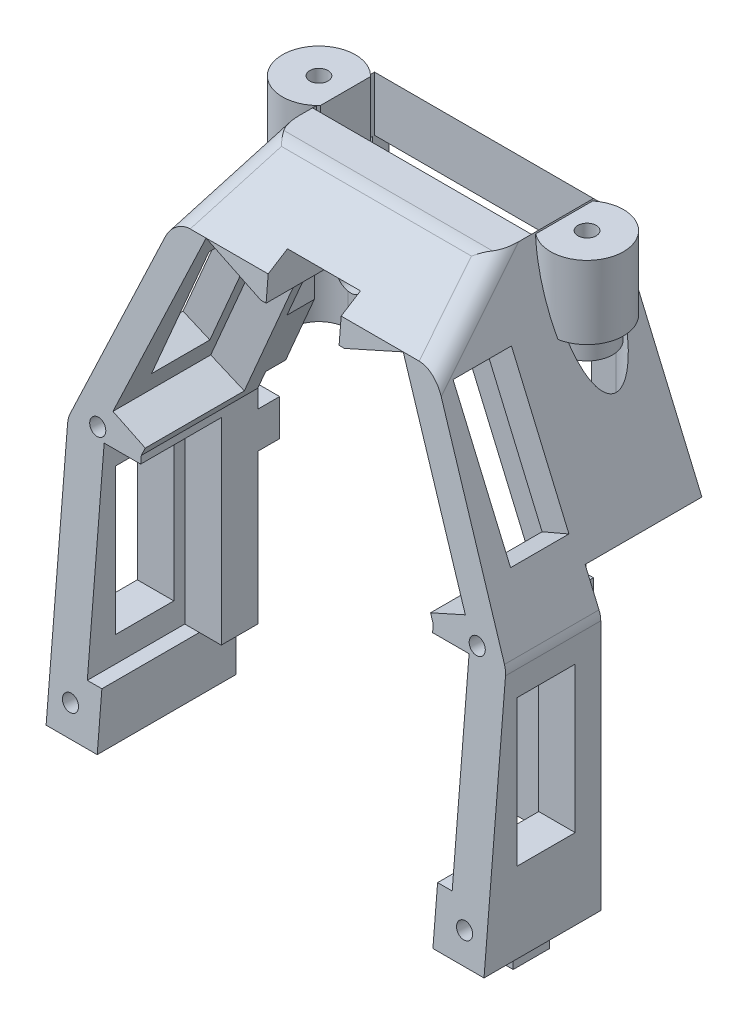
SolidWorks part; units mm, degrees
ref_plane "Front Plane" through (0, 0, 0) normal (0, 0, 1) x (1, 0, 0)
ref_plane "Top Plane" through (0, 0, 0) normal (0, 1, 0) x (1, 0, 0)
ref_plane "Right Plane" through (0, 0, 0) normal (1, 0, 0) x (0, 0, -1)
sketch "Sketch1" plane through (0, 0, 0) normal (0, 0, 1) x (1, 0, 0)
  line L0 (-30, 17.5) -> (-15, 52.5)
  line L2 (-30, -17.5) -> (-30, 17.5)
  line L4 (30, -17.5) -> (30, 17.5)
  line L5 (-30, -17.5) -> (30, 17.5) construction
  line L6 (-30, 17.5) -> (30, -17.5) construction
  line L7 (-15, 52.5) -> (15, 52.5)
  line L8 (15, 52.5) -> (30, 17.5)
  line L9 (-20, -17.5) -> (-20, 15.4474)
  line L10 (-20, 15.4474) -> (-8.406, 42.5)
  line L11 (-8.406, 42.5) -> (8.406, 42.5)
  line L12 (8.406, 42.5) -> (20, 15.4474)
  line L13 (20, -17.5) -> (20, 15.4474)
  line L14 (-30, -17.5) -> (-20, -17.5)
  line L15 (20, -17.5) -> (30, -17.5)
  point P0 (0, 0)
  point P9 (0, 52.5)
  dimension "D1" = 60
  dimension "D2" = 35
  dimension "D3" = 70
  dimension "D4" = 30
  dimension "D5" = 10
extrude "Boss-Extrude1" add sketch "Sketch1" along normal blind 32
sketch "Sketch2" plane through (0, 0, 0) normal (0, 1, 0) x (1, 0, 0)
  line L0 (15, 0) -> (-15, 0) construction
  line L1 (15, -2) -> (-15, -2)
  line L2 (15, -2) -> (15, -10.5)
  line L3 (15, -10.5) -> (-15, -10.5)
  line L4 (-15, -2) -> (-15, -10.5)
  point P9 (0, -2)
  dimension "D1" = 8.5
  dimension "D2" = 2
  dimension "D3" = 30
extrude "Cut-Extrude1" cut sketch "Sketch2" against normal blind 25 from surface starting at face at (0, 52.5, 16)
sketch "Sketch3" plane through (0, 0, 0) normal (0, 1, 0) x (1, 0, 0)
  line L0 (-15, 0) -> (-30, 0) construction
  line L1 (15, -14) -> (-15, -14)
  line L2 (15, -14) -> (15, 0)
  line L3 (15, 0) -> (-15, 0)
  line L4 (-15, -14) -> (-15, 0)
  line L5 (15, -14) -> (-15, 0) construction
  line L6 (15, 0) -> (-15, -14) construction
  line L7 (0, -7) -> (0, 0) construction
  line L8 (18.37, -6.25) -> (-18.37, -6.25) construction
  line L9 (18.37, -10.25) -> (-18.37, -10.25)
  line L10 (18.37, -2.25) -> (-18.37, -2.25)
  line L11 (15, -10.5) -> (-15, -2) construction
  arc A2 (18.37, -10.25) -> (18.37, -2.25) centre (18.37, -6.25) ccw
  arc A3 (-18.37, -2.25) -> (-18.37, -10.25) centre (-18.37, -6.25) ccw
  point P0 (0, -7)
  point P7 (0, -14)
  point P13 (0, -6.25)
  dimension "D4" = 8
  dimension "D3" = 3.37
  dimension "D1" = 30
  dimension "D2" = 14
extrude "Cut-Extrude3" cut sketch "Sketch3" along normal blind 25 from offset 20 contours L9 A3 L10 A2 | L1 L4 L3 L2
sketch "Sketch4" plane through (0, 0, 0) normal (0, 0, 1) x (1, 0, 0)
  line L0 (-8.406, 42.5) -> (8.406, 42.5) construction
  line L1 (-5, 42.5) -> (5, 42.5)
  line L2 (-5, 42.5) -> (-5, 47.5)
  line L3 (-5, 47.5) -> (5, 47.5)
  line L4 (5, 42.5) -> (5, 47.5)
  point P6 (0, 47.5)
  dimension "D1" = 10
  dimension "D2" = 5
extrude "Cut-Extrude4" cut sketch "Sketch4" against normal up to surface (-10.5 mm away) from surface up to face at (0, 48.75, 10.5) starting at face at (0, 15.4912, 32)
sketch "Sketch5" plane through (0, 0, 0) normal (1, 0, 0) x (0, 0, -1)
  line L0 (-32, -17.5) -> (-32, 17.5) construction
  line L1 (-27.5, -6.5) -> (-19.5, -6.5)
  line L2 (-27.5, -6.5) -> (-27.5, 13.5)
  line L3 (-27.5, 13.5) -> (-19.5, 13.5)
  line L4 (-19.5, -6.5) -> (-19.5, 13.5)
  line L5 (-27.5, -6.5) -> (-19.5, 13.5) construction
  line L6 (-27.5, 13.5) -> (-19.5, -6.5) construction
  line L7 (-32, -17.5) -> (0, -17.5) construction
  line L9 (0, -17.5) -> (-13, -17.5)
  line L10 (0, -17.5) -> (0, 20.5)
  line L11 (0, 20.5) -> (-13, 20.5)
  line L12 (-13, -17.5) -> (-13, 20.5)
  point P0 (-23.5, 3.5)
  dimension "D1" = 8
  dimension "D2" = 20
  dimension "D3" = 4.5
  dimension "D4" = 11
  dimension "D5" = 13
  dimension "D6" = 38
extrude "Cut-Extrude5" cut sketch "Sketch5" against normal up to surface (30 mm away) from surface up to face at (-30, 0, 16) starting at face at (30, 0, 16)
sketch "Sketch6" plane through (0, 0, 0) normal (1, 0, 0) x (0, 0, -1)
  line L0 (-27.5, -6.5) -> (-27.5, 13.5) construction
  line L1 (-32, -17.5) -> (-32, 17.5) construction
  line L2 (-18, -10) -> (-32, -10)
  line L3 (-18, -10) -> (-18, 17)
  line L4 (-18, 17) -> (-32, 17)
  line L5 (-32, -10) -> (-32, 17)
  line L6 (-18, -10) -> (-32, 17) construction
  line L7 (-18, 17) -> (-32, -10) construction
  point P4 (-25, 3.5)
  point P11 (-27.5, 3.5)
  dimension "D1" = 27
  dimension "D2" = 14
extrude "Cut-Extrude6" cut sketch "Sketch6" against normal mid plane 50
sketch "Sketch7" plane through (0, 0, 0) normal (1, 0, 0) x (0, 0, -1)
  line L1 (0, -17.5) -> (-16, -17.5)
  line L2 (0, -17.5) -> (0, 22.5)
  line L3 (0, 22.5) -> (-16, 22.5)
  line L4 (-16, -17.5) -> (-16, 22.5)
  line L6 (-32, -17.5) -> (-13, -17.5) construction
  line L7 (0, 52.5) -> (0, 20.5) construction
  dimension "D1" = 16
  dimension "D2" = 40
extrude "Cut-Extrude7" cut sketch "Sketch7" along normal blind 5 from surface starting at face at (-30, 3.5, 23.5)
extrude "Cut-Extrude8" cut sketch "Sketch7<2>" against normal blind 5 from surface starting at face at (30, 3.5, 23.5)
sketch "Sketch7<2>" plane through (0, 0, 0) normal (1, 0, 0) x (0, 0, -1) same geometry as "Sketch7"
ref_plane "Plane1" through (-40.8725, 17.5168, 0) normal (-0.9191, 0.3939, 0) x (0, 0, 1)
sketch "Sketch8" plane through (-40.8725, 17.5168, 0) normal (-0.9191, 0.3939, 0) x (0, 0, 1)
  line L0 (32, 42.3463) -> (32, 4.2675) construction
  line L1 (16.8, 33.3069) -> (24.8, 33.3069)
  line L2 (16.8, 33.3069) -> (16.8, 13.3069)
  line L3 (16.8, 13.3069) -> (24.8, 13.3069)
  line L4 (24.8, 33.3069) -> (24.8, 13.3069)
  line L5 (16.8, 33.3069) -> (24.8, 13.3069) construction
  line L6 (16.8, 13.3069) -> (24.8, 33.3069) construction
  point P0 (20.8, 23.3069)
  point P8 (32, 23.3069)
  dimension "D1" = 8
  dimension "D2" = 20
  dimension "D3" = 7.2
extrude "Cut-Extrude9" cut sketch "Sketch8" against normal blind 15 from surface starting at face at (-19.2921, 42.485, 6.25)
ref_plane "Plane2" through (40.8725, 17.5168, 0) normal (0.9191, 0.3939, 0) x (0, 0, -1)
sketch "Sketch9" plane through (40.8725, 17.5168, 0) normal (0.9191, 0.3939, 0) x (0, 0, -1)
  line L0 (-32, 4.2675) -> (-32, 42.3463) construction
  line L1 (-24.8, 13.3069) -> (-16.8, 13.3069)
  line L2 (-24.8, 13.3069) -> (-24.8, 33.3069)
  line L3 (-24.8, 33.3069) -> (-16.8, 33.3069)
  line L4 (-16.8, 13.3069) -> (-16.8, 33.3069)
  line L5 (-24.8, 13.3069) -> (-16.8, 33.3069) construction
  line L6 (-24.8, 33.3069) -> (-16.8, 13.3069) construction
  point P0 (-20.8, 23.3069)
  point P7 (-32, 23.3069)
  dimension "D1" = 8
  dimension "D2" = 20
  dimension "D3" = 7.2
extrude "Cut-Extrude10" cut sketch "Sketch9" against normal blind 15 from surface starting at face at (19.2921, 42.485, 6.25)
sketch "Sketch11" plane through (-40.8725, 17.5168, 0) normal (-0.9191, 0.3939, 0) x (0, 0, 1)
  line L0 (24.8, 33.3069) -> (24.8, 13.3069) construction
  line L1 (15.3, 36.8069) -> (32, 36.8069)
  line L2 (15.3, 36.8069) -> (15.3, 9.8069)
  line L3 (15.3, 9.8069) -> (32, 9.8069)
  line L4 (32, 36.8069) -> (32, 9.8069)
  line L5 (32, 42.3463) -> (32, 4.2675) construction
  point P6 (24.8, 23.3069)
  point P7 (32, 23.3069)
  dimension "D1" = 27
  dimension "D2" = 16.7
extrude "Cut-Extrude11" cut sketch "Sketch11" against normal blind 15 from offset 14 offset against normal yes
sketch "Sketch12" plane through (40.8725, 17.5168, 0) normal (0.9191, 0.3939, 0) x (0, 0, -1)
  line L1 (-15.3, 9.8069) -> (-32, 9.8069)
  line L2 (-15.3, 9.8069) -> (-15.3, 36.8069)
  line L3 (-15.3, 36.8069) -> (-32, 36.8069)
  line L4 (-32, 9.8069) -> (-32, 36.8069)
  line L5 (-15.3, 9.8069) -> (-32, 36.8069) construction
  line L6 (-15.3, 36.8069) -> (-32, 9.8069) construction
  line L7 (-24.8, 13.3069) -> (-24.8, 33.3069) construction
  line L8 (-32, 4.2675) -> (-32, 42.3463) construction
  point P0 (-23.65, 23.3069)
  point P10 (-24.8, 23.3069)
  dimension "D1" = 27
  dimension "D2" = 16.7
extrude "Cut-Extrude12" cut sketch "Sketch12" against normal blind 16 from offset 14 offset against normal yes
sketch "Sketch13" plane through (0, 0, 0) normal (1, 0, 0) x (0, 0, -1)
  line L0 (-32, 52.5) -> (-26, 52.5)
  line L1 (-32, 52.5) -> (-10.5, 52.5) construction
  line L2 (-26, 52.5) -> (-32, -17.5)
  line L3 (-32, -17.5) -> (-32, 52.5)
  dimension "D1" = 6
extrude "Cut-Extrude13" cut sketch "Sketch13" against normal mid plane 62
sketch "Sketch14" plane through (0, 0, 0) normal (1, 0, 0) x (0, 0, -1)
  line L0 (-16, 52.5) -> (-26, 52.5)
  line L1 (-26, 52.5) -> (-10.5, 52.5) construction
  line L2 (-26, 52.5) -> (-26.5715, 45.8328)
  line L3 (-26.5715, 45.8328) -> (-16, 52.5)
  dimension "D1" = 10
extrude "Cut-Extrude14" cut sketch "Sketch14" against normal mid plane 62
sketch "Sketch16" plane through (0, 0, 0) normal (0, 1, 0) x (1, 0, 0)
  circle A0 centre (18.37, -6.25) radius 3.5
  circle A1 centre (-18.37, -6.25) radius 3.5
  circle A2 centre (18.37, -6.25) radius 1.25
  circle A3 centre (-18.37, -6.25) radius 1.25
  arc A4 (-18.37, -2.25) -> (-18.37, -10.25) centre (-18.37, -6.25) ccw construction
  arc A5 (18.37, -10.25) -> (18.37, -2.25) centre (18.37, -6.25) ccw construction
  dimension "D1" = 2.5
  dimension "D2" = 2.5
  dimension "D3" = 7
extrude "Boss-Extrude2" add sketch "Sketch16" against normal blind 5.5 from surface starting at face at (16.6071, 45, 6.25)
ref_plane "Plane3" through (0, 3.4492, 40.241) normal (0, 0.0854, 0.9963) x (1, 0, 0)
sketch "Sketch17" plane through (0, 3.4492, 40.241) normal (0, 0.0854, 0.9963) x (1, 0, 0)
  line L1 (-30, -20.1689) -> (-20, -20.1689) construction
  line L2 (-30, -20.1689) -> (-30, 14.9594) construction
  line L3 (0, 0) -> (0, 14.6383) construction
  circle A0 centre (-27, -16.1689) radius 1.1
  circle A1 centre (-26, 15.8311) radius 1.1
  circle A2 centre (27, -16.1689) radius 1.1
  circle A3 centre (26, 15.8311) radius 1.1
  dimension "D1" = 2.2
  dimension "D2" = 4
  dimension "D3" = 3
  dimension "D4" = 4
  dimension "D5" = 32
extrude "Cut-Extrude15" cut sketch "Sketch17" against normal blind 10 from surface starting at face at (-22.1332, 11.6213, 29.5039)
fillet "Fillet3" radius 3 5 edges at (-30, 17.5, 22.5) (30, 17.5, 22.5) (16.4287, 49.1664, 21.2857) (-16.4287, 49.1664, 21.2857) (0, 52.5, 16)
chamfer "Chamfer1" distance 2 angle 45 1 edges at (0, 52.5, 0)
sketch "Sketch18" plane through (0, 0, 0) normal (0, 0, 1) x (1, 0, 0)
  line L0 (30, 16.8842) -> (30, -17.5) construction
  line L1 (25, -17.5) -> (30, -17.5) construction
  line L2 (0, 0) -> (0, 26.5) construction
  circle A0 centre (18, 26.5) radius 1.6
  circle A2 centre (-18, 26.5) radius 1.6
  dimension "D1" = 12
  dimension "D2" = 44
  dimension "D3" = 3.2
extrude "Cut-Extrude16" cut sketch "Sketch18" along normal blind 6
sketch "Sketch19" plane through (0, 0, 0) normal (0, 0, 1) x (1, 0, 0)
  line L0 (-25, -10) -> (-20, -10) construction
  line L1 (-20, -17.5) -> (-23, -17.5)
  line L2 (-20, -17.5) -> (-20, -10)
  line L3 (-20, -10) -> (-23, -10)
  line L4 (-23, -17.5) -> (-23, -10)
  line L5 (20, -10) -> (25, -10) construction
  line L6 (20, -17.5) -> (23, -17.5)
  line L7 (20, -17.5) -> (20, -10)
  line L8 (20, -10) -> (23, -10)
  line L9 (23, -17.5) -> (23, -10)
  dimension "D1" = 3
  dimension "D2" = 3
extrude "Cut-Extrude17" cut sketch "Sketch19" along normal blind 19 from surface starting at face at (-21.5669, 4.2895, 13)
sketch "Sketch21" plane through (0, 0, 0) normal (0, 1, 0) x (1, 0, 0)
  line L0 (-25, -16) -> (-30, -16) construction
  line L1 (-28, -26) -> (-26, -26)
  line L2 (-28, -26) -> (-28, -21)
  line L3 (-28, -21) -> (-26, -21)
  line L4 (-26, -26) -> (-26, -21)
  line L5 (-28, -26) -> (-26, -21) construction
  line L6 (-28, -21) -> (-26, -26) construction
  line L7 (-30, -32) -> (-30, -16) construction
  line L8 (0, 0) -> (0, -23.9279) construction
  line L9 (-5, -23.9279) -> (5, -23.9279) construction
  line L10 (28, -21) -> (26, -21)
  line L11 (28, -26) -> (28, -21)
  line L12 (28, -26) -> (26, -26)
  line L13 (26, -26) -> (26, -21)
  point P0 (-27, -23.5)
  point P9 (-30, -24)
  dimension "D1" = 2
  dimension "D2" = 5
  dimension "D3" = 5
  dimension "D4" = 2
extrude "Boss-Extrude4" add sketch "Sketch21" against normal blind 3 from surface starting at face at (-26, -17.5, 20.3333)
sketch "Sketch22" plane through (0, 0, 0) normal (0, 0, 1) x (1, 0, 0)
  line L0 (-25, 20.5) -> (-17.8346, 20.5) construction
  line L1 (-23, 15.5) -> (-20, 15.5)
  line L2 (-23, 15.5) -> (-23, 10.5)
  line L3 (-23, 10.5) -> (-20, 10.5)
  line L4 (-20, 15.5) -> (-20, 10.5)
  line L5 (-23, 15.5) -> (-20, 10.5) construction
  line L6 (-23, 10.5) -> (-20, 15.5) construction
  line L7 (-25, -17.5) -> (-25, 20.5) construction
  line L8 (0, 0) -> (0, 20.6704) construction
  line L9 (23, 10.5) -> (20, 10.5)
  line L10 (20, 15.5) -> (20, 10.5)
  line L11 (23, 15.5) -> (20, 15.5)
  line L12 (23, 15.5) -> (23, 10.5)
  point P0 (-21.5, 13)
  dimension "D1" = 5
  dimension "D2" = 5
  dimension "D3" = 2
  dimension "D4" = 3
extrude "Boss-Extrude5" add sketch "Sketch22" against normal blind 3 from surface starting at face at (-21.9764, 0.2068, 13)
sketch "Sketch23" plane through (0, 0, 0) normal (0, 0, 1) x (1, 0, 0)
  line L0 (-16.0633, 17.5539) -> (-19.5456, 19.0463)
  line L1 (-24.1413, 21.0159) -> (-18.6265, 18.6523) construction
  line L2 (-19.5456, 19.0463) -> (-8.9098, 43.8632)
  line L3 (-5.4275, 42.3708) -> (-8.9098, 43.8632)
  line L5 (-5.4275, 42.3708) -> (-16.0633, 17.5539)
  line L6 (0, 0) -> (0, 20.6454) construction
  line L7 (16.0633, 17.5539) -> (19.5456, 19.0463)
  line L8 (19.5456, 19.0463) -> (8.9098, 43.8632)
  line L9 (8.9098, 43.8632) -> (5.4275, 42.3708)
  line L10 (5.4275, 42.3708) -> (16.0633, 17.5539)
  line L14 (-8.406, 42.5) -> (-18.6265, 18.6523) construction
  line L15 (-5.729, 42.5) -> (-13.5055, 45.8328) construction
  dimension "D1" = 1
extrude "Cut-Extrude18" cut sketch "Sketch23" against normal blind 6 from surface starting at face at (-14.0817, 34.1002, 15.3)
sketch "Sketch24" plane through (0, 0, 0) normal (0, 0, 1) x (1, 0, 0)
  line L6 (0, 0) -> (0, 25.9881) construction
  line L11 (-20, 15.4474) -> (-20, 17.986)
  line L12 (-20, 17.986) -> (-19.0769, 20.1398)
  line L13 (-8.9098, 43.8632) -> (-19.5456, 19.0463) construction
  line L14 (-20, 15.4474) -> (-18.1605, 19.7396)
  line L15 (-18.1605, 19.7396) -> (-19.0769, 20.1398)
  line L16 (-18.6265, 18.6523) -> (-19.3346, 17) construction
  line L17 (20, 15.4474) -> (18.1605, 19.7396)
  line L18 (20, 15.4474) -> (20, 17.986)
  line L19 (20, 17.986) -> (19.0769, 20.1398)
  line L20 (18.1605, 19.7396) -> (19.0769, 20.1398)
extrude "Cut-Extrude20" cut sketch "Sketch24" along normal blind 42
sketch "Sketch25" plane through (0, 0, 0) normal (0, 1, 0) x (1, 0, 0)
  line L0 (-15, -7.195) -> (-15, -5.305)
  line L1 (15, -7.195) -> (15, -5.305)
  arc A0 (-15, -7.195) -> (-15, -5.305) centre (-18.37, -6.25) ccw
  arc A1 (15, -5.305) -> (15, -7.195) centre (18.37, -6.25) ccw
extrude "Cut-Extrude21" cut sketch "Sketch25" along normal blind 10 from surface starting at face at (-18.37, 39.5, 7.5)
sketch "Sketch26" plane through (0, 0, 0) normal (0, 1, 0) x (1, 0, 0)
  line L0 (-14.7408, -9.6893) -> (-14.7408, -2.8107)
  line L1 (15.238, -10.1475) -> (15.238, -2.3525)
  arc A0 (-14.7408, -2.8107) -> (-14.7408, -9.6893) centre (-18.37, -6.25) ccw
  arc A1 (15.238, -10.1475) -> (15.238, -2.3525) centre (18.37, -6.25) ccw
  circle A2 centre (18.37, -6.25) radius 1.25
  circle A3 centre (-18.37, -6.25) radius 1.25
  dimension "D1" = 10
extrude "Boss-Extrude6" add sketch "Sketch26" against normal blind 10 from surface starting at face at (0, 52.5, 12.6924)
